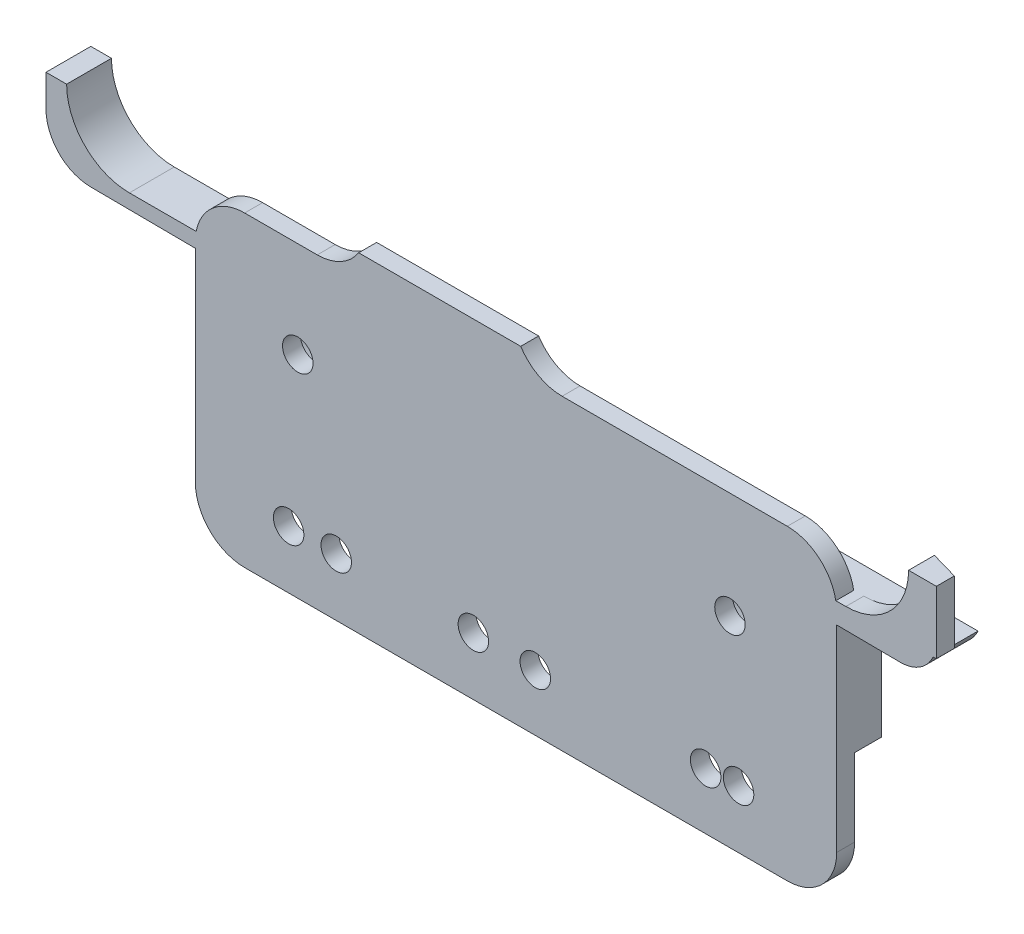
SolidWorks part; units mm, degrees
ref_plane "Plan de face" through (0, 0, 0) normal (0, 0, 1) x (1, 0, 0)
ref_plane "Plan de dessus" through (0, 0, 0) normal (0, 1, 0) x (1, 0, 0)
ref_plane "Plan de droite" through (0, 0, 0) normal (1, 0, 0) x (0, 0, -1)
sketch "Esquisse1" plane through (0, 0, 0) normal (0, 0, 1) x (1, 0, 0)
  line L0 (-101.8864, 22.7193) -> (-64.9263, 22.7193) construction
  line L1 (-68.0864, 83.4017) -> (-68.0864, 71.4017) construction
  line L2 (-118.8906, -27.2807) -> (-47.3665, -27.2807) construction
  line L3 (-120.7144, 72.7193) -> (-45.5428, 72.7193) construction
  line L4 (-83.4864, -42.5983) -> (-83.4864, 89.4017) construction
  line L5 (-56.8564, -27.2807) -> (-56.8564, 72.7193) construction
  line L6 (-110.1164, -27.2807) -> (-110.1164, 72.7193) construction
  line L7 (-59.2664, -27.2807) -> (-59.2664, 72.7193) construction
  line L8 (-56.8564, -13.2807) -> (-110.1164, -13.2807) construction
  line L9 (-64.3564, -27.2807) -> (-64.3564, 72.7193) construction
  line L10 (-110.1164, 36.7193) -> (-56.8564, 36.7193) construction
  line L11 (-56.8564, 66.9393) -> (-110.1164, 66.9393) construction
  line L12 (-91.8564, -27.2807) -> (-91.8564, 72.7193) construction
  line L13 (-107.4664, -27.2807) -> (-107.4664, 72.7193) construction
  line L14 (-56.8564, -14.5207) -> (-110.1164, -14.5207) construction
  line L15 (-110.1164, 60.7193) -> (-56.8564, 60.7193) construction
  line L16 (-117.6801, 66.9393) -> (-117.6801, 59.6951)
  line L17 (-112.1801, 54.1951) -> (-105.2942, 54.1951)
  line L18 (-99.7942, 48.6951) -> (-99.7942, 35.9308)
  line L19 (-113.3906, -38.0606) -> (-52.8665, -38.0606)
  line L20 (-105.2942, -3.8078) -> (-113.3906, -3.8078)
  line L21 (-118.8906, -9.3078) -> (-118.8906, -18.422)
  line L23 (-47.3665, -18.422) -> (-47.3665, -9.3078)
  line L24 (-52.8665, -3.8078) -> (-77.9864, -3.8078)
  line L25 (-83.4864, 1.6922) -> (-83.4864, 12.91)
  line L26 (-77.9864, 60.7193) -> (-54.1904, 60.7193)
  line L27 (-48.6904, 66.2193) -> (-48.6904, 67.2193)
  line L28 (-54.1904, 72.7193) -> (-112.1801, 72.7193)
  line L29 (-117.6801, 67.2193) -> (-117.6801, 66.9393)
  line L30 (-105.2942, 30.4308) -> (-112.1801, 30.4308)
  line L31 (-117.6801, 24.9308) -> (-117.6801, 23.91)
  line L32 (-112.1801, 18.41) -> (-105.2942, 18.41)
  line L33 (-77.9864, 30.4308) -> (-69.8564, 30.4308)
  line L34 (-64.3564, 24.9308) -> (-64.3564, 23.91)
  line L35 (-69.8564, 18.41) -> (-77.9864, 18.41)
  line L36 (-99.7942, 12.91) -> (-99.7942, 1.6922)
  line L37 (-111.3906, 21.4601) -> (-70.0864, 21.4601)
  line L38 (-113.3906, 23.4601) -> (-113.3906, 24.8425)
  line L39 (-111.3906, 26.8425) -> (-70.0864, 26.8425)
  line L40 (-68.0864, 23.4601) -> (-68.0864, 24.8425)
  line L41 (-83.4864, 35.9308) -> (-83.4864, 55.2193)
  line L42 (-118.8906, -18.422) -> (-118.8906, -32.5606)
  line L43 (-47.3665, -18.422) -> (-47.3665, -32.5606)
  circle A0 centre (-59.2664, -15.6637) radius 1.7
  arc A1 (-77.9864, 30.4308) -> (-83.4864, 35.9308) centre (-77.9864, 35.9308) cw
  circle A2 centre (-59.2664, 66.9393) radius 1.7
  circle A3 centre (-91.8564, 36.7193) radius 1.7
  arc A4 (-64.3564, 23.91) -> (-69.8564, 18.41) centre (-69.8564, 23.91) cw
  arc A5 (-112.1801, 72.7193) -> (-117.6801, 67.2193) centre (-112.1801, 67.2193) ccw
  circle A6 centre (-107.4664, -14.5207) radius 1.7
  circle A7 centre (-107.4664, 60.7193) radius 1.7
  arc A8 (-117.6801, 59.6951) -> (-112.1801, 54.1951) centre (-112.1801, 59.6951) ccw
  arc A9 (-105.2942, 54.1951) -> (-99.7942, 48.6951) centre (-105.2942, 48.6951) cw
  arc A10 (-99.7942, 1.6922) -> (-105.2942, -3.8078) centre (-105.2942, 1.6922) cw
  arc A11 (-113.3906, -3.8078) -> (-118.8906, -9.3078) centre (-113.3906, -9.3078) ccw
  arc A14 (-47.3665, -9.3078) -> (-52.8665, -3.8078) centre (-52.8665, -9.3078) ccw
  arc A15 (-77.9864, -3.8078) -> (-83.4864, 1.6922) centre (-77.9864, 1.6922) cw
  arc A16 (-83.4864, 55.2193) -> (-77.9864, 60.7193) centre (-77.9864, 55.2193) cw
  arc A17 (-54.1904, 60.7193) -> (-48.6904, 66.2193) centre (-54.1904, 66.2193) ccw
  arc A18 (-48.6904, 67.2193) -> (-54.1904, 72.7193) centre (-54.1904, 67.2193) ccw
  arc A19 (-69.8564, 30.4308) -> (-64.3564, 24.9308) centre (-69.8564, 24.9308) cw
  arc A20 (-77.9864, 18.41) -> (-83.4864, 12.91) centre (-77.9864, 12.91) ccw
  arc A21 (-105.2942, 18.41) -> (-99.7942, 12.91) centre (-105.2942, 12.91) cw
  arc A22 (-117.6801, 23.91) -> (-112.1801, 18.41) centre (-112.1801, 23.91) ccw
  arc A23 (-112.1801, 30.4308) -> (-117.6801, 24.9308) centre (-112.1801, 24.9308) ccw
  arc A24 (-105.2942, 30.4308) -> (-99.7942, 35.9308) centre (-105.2942, 35.9308) ccw
  arc A25 (-70.0864, 26.8425) -> (-68.0864, 24.8425) centre (-70.0864, 24.8425) cw
  arc A26 (-70.0864, 21.4601) -> (-68.0864, 23.4601) centre (-70.0864, 23.4601) ccw
  arc A27 (-111.3906, 21.4601) -> (-113.3906, 23.4601) centre (-111.3906, 23.4601) cw
  arc A28 (-113.3906, 24.8425) -> (-111.3906, 26.8425) centre (-111.3906, 24.8425) cw
  circle A29 centre (-58.3064, -31.6037) radius 1.7
  circle A30 centre (-108.4864, -31.6007) radius 1.7
  arc A31 (-47.3665, -32.5606) -> (-52.8665, -38.0606) centre (-52.8665, -32.5606) cw
  arc A32 (-118.8906, -32.5606) -> (-113.3906, -38.0606) centre (-113.3906, -32.5606) ccw
  point P61 (-117.6801, 72.7193)
  point P68 (-99.7942, -3.8078)
  point P79 (-83.4864, -3.8078)
  point P82 (-83.4864, 60.7193)
  point P87 (-48.6904, 72.7193)
  point P98 (-83.4864, 30.4308)
  point P101 (-64.3564, 18.41)
  point P104 (-64.3564, 30.4308)
  point P109 (-99.7942, 18.41)
  point P116 (-99.7942, 30.4308)
  dimension "D1" = 5.5
  dimension "D2" = 5.5
  dimension "D3" = 2
  dimension "D8" = 5.5
  dimension "D4" = 15.94
  dimension "D5" = 17.08
  dimension "D6" = 0.96
  dimension "D7" = 1.02
extrude "Boss.-Extru.1" add sketch "Esquisse1" along normal blind 3
sketch "Esquisse2" plane through (0, 0, 0) normal (0, 0, -1) x (-1, 0, 0)
  line L0 (39.3464, 87.1044) -> (39.3464, -42.3137) construction
  line L1 (133.2464, 87.1044) -> (133.2464, 37.9772) construction
  line L2 (59.2664, -15.6637) -> (59.2664, 1.7249) construction
  line L3 (133.2464, -8.2937) -> (39.3464, -8.2937) construction
  line L4 (133.2464, 54.4563) -> (39.3464, 54.4563) construction
  line L5 (126.2464, -8.2937) -> (126.2464, -1.2937) construction
  line L6 (126.2464, -1.2937) -> (133.2464, -1.2937) construction
  line L7 (126.2464, 54.4563) -> (126.2464, 47.4563) construction
  line L8 (126.2464, 47.4563) -> (133.2464, 47.4563) construction
  line L9 (46.3464, 54.4563) -> (46.3464, 47.4563) construction
  line L10 (46.3464, 47.4563) -> (39.3464, 47.4563) construction
  line L11 (39.3464, -1.2937) -> (46.3464, -1.2937) construction
  line L12 (46.3464, -1.2937) -> (46.3464, -8.2937) construction
  line L13 (118.8906, -9.9695) -> (130.5846, -9.8801)
  line L14 (117.6801, 57.0999) -> (130.5464, 57.0999)
  line L15 (47.3665, -10.5841) -> (47.3665, -23.922)
  line L16 (36.2569, 53.0999) -> (36.2569, 47.4563)
  line L17 (36.2569, 47.4563) -> (39.3464, 47.4563)
  line L18 (39.3464, -1.2937) -> (36.2482, -1.2937)
  line L19 (36.2482, -1.2937) -> (36.2482, -6.6454)
  line L20 (40.2828, -10.6453) -> (47.3665, -10.5841)
  line L21 (48.6904, 60.7193) -> (48.6904, 72.7193)
  line L22 (48.6904, 60.7193) -> (48.6904, 57.0999)
  line L23 (126.2464, 54.4563) -> (46.3464, 54.4563)
  line L24 (46.3464, -8.2937) -> (126.2464, -8.2937)
  line L25 (133.2464, 47.4563) -> (133.2464, 40.9772)
  line L26 (48.6904, 72.7193) -> (117.6801, 72.7193)
  line L27 (138.5464, 8.4156) -> (145.7527, 8.4156)
  line L28 (40.2569, 57.0999) -> (48.6904, 57.0999)
  line L29 (148.7527, 11.4156) -> (148.7527, 38.1792)
  line L30 (133.2464, 34.4495) -> (133.2464, -42.3137) construction
  line L32 (117.6801, 72.7193) -> (117.6801, 57.0999)
  line L35 (135.5464, -24.0475) -> (135.5464, 64.4693) construction
  line L36 (47.3665, -32.5606) -> (47.3665, -9.3078) construction
  line L37 (133.2464, 8.3631) -> (133.2464, -1.2937)
  line L38 (47.3665, -23.922) -> (118.8906, -23.922)
  line L39 (118.8906, -23.922) -> (118.8906, -9.9695)
  line L40 (118.8906, -9.3078) -> (118.8906, -32.5606) construction
  line L41 (145.7527, 41.1792) -> (138.5464, 41.1792)
  line L42 (136.2464, 11.3631) -> (142.1623, 11.3631)
  line L43 (145.1623, 14.3631) -> (145.1623, 34.9772)
  line L44 (142.1623, 37.9772) -> (136.2464, 37.9772)
  line L47 (135.5464, -4.8802) -> (135.5464, 5.4156)
  line L57 (135.5464, 44.1792) -> (135.5464, 52.0999)
  arc A0 (133.2464, -1.2937) -> (126.2464, -8.2937) centre (126.2464, -1.2937) cw
  arc A1 (133.2464, 47.4563) -> (126.2464, 54.4563) centre (126.2464, 47.4563) ccw
  arc A2 (46.3464, 54.4563) -> (39.3464, 47.4563) centre (46.3464, 47.4563) ccw
  arc A3 (39.3464, -1.2937) -> (46.3464, -8.2937) centre (46.3464, -1.2937) ccw
  arc A4 (40.2569, 57.0999) -> (36.2569, 53.0999) centre (40.2569, 53.0999) ccw
  arc A5 (148.7527, 38.1792) -> (145.7527, 41.1792) centre (145.7527, 38.1792) ccw
  arc A6 (138.5464, 41.1792) -> (135.5464, 44.1792) centre (138.5464, 44.1792) cw
  arc A7 (136.2464, 37.9772) -> (133.2464, 40.9772) centre (136.2464, 40.9772) cw
  arc A8 (145.1623, 34.9772) -> (142.1623, 37.9772) centre (142.1623, 34.9772) ccw
  arc A9 (142.1623, 11.3631) -> (145.1623, 14.3631) centre (142.1623, 14.3631) ccw
  arc A10 (145.7527, 8.4156) -> (148.7527, 11.4156) centre (145.7527, 11.4156) ccw
  arc A11 (133.2464, 8.3631) -> (136.2464, 11.3631) centre (136.2464, 8.3631) cw
  arc A12 (135.5464, 52.0999) -> (130.5464, 57.0999) centre (130.5464, 52.0999) ccw
  arc A13 (138.5464, 8.4156) -> (135.5464, 5.4156) centre (138.5464, 5.4156) ccw
  arc A15 (130.5846, -9.8801) -> (135.5464, -4.8802) centre (130.5464, -4.8802) ccw
  arc A16 (36.2482, -6.6454) -> (40.2828, -10.6453) centre (40.2482, -6.6454) ccw
  circle A17 centre (59.2664, -15.6637) radius 5.2
  circle A18 centre (107.4664, -14.5207) radius 5.2
  circle A19 centre (107.4664, 60.7193) radius 5.2
  circle A20 centre (59.2664, 66.9393) radius 5.2
  point P34 (135.5464, 57.0999)
  point P37 (132.9964, 22.9063)
  point P43 (132.9964, 22.9063)
  point P45 (133.2464, 29.4495)
  point P50 (133.2464, 16.3631)
  point P62 (111.5444, -10.0296)
  point P71 (64.0892, -10.4396)
  point P74 (135.5464, 26.097)
  point P75 (134.7715, 19.7156)
  point P107 (135.5464, 19.7156)
  point P110 (135.5464, -9.8421)
  dimension "D13" = 4
  dimension "D14" = 3
  dimension "D16" = 5
  dimension "D1" = 19.92
  dimension "D2" = 93.9
  dimension "D3" = 7.37
  dimension "D4" = 62.75
  dimension "D5" = 7
  dimension "D6" = 7
  dimension "D7" = 7
  dimension "D8" = 7
  dimension "D9" = 7
  dimension "D10" = 7
  dimension "D11" = 7
  dimension "D12" = 7
  dimension "D17" = 2.3
extrude "Boss.-Extru.2" add sketch "Esquisse2" along normal blind 3 and the other way blind 3
sketch "Esquisse5" plane through (0, 0, 3) normal (0, 0, 1) x (1, 0, 0)
  line L1 (-156.3908, -45.761) -> (-27.0007, -45.761)
  line L2 (-156.3908, -45.761) -> (-156.3908, 79.8705)
  line L3 (-156.3908, 79.8705) -> (-27.0007, 79.8705)
  line L4 (-27.0007, -45.761) -> (-27.0007, 79.8705)
extrude "Enlèv. mat.-Extru.2" cut sketch "Esquisse5" against normal blind 1
sketch "Esquisse6" plane through (0, 0, 2) normal (0, 0, 1) x (1, 0, 0)
  line L0 (-69.6235, 64.7274) -> (-83.6235, 64.7274) construction
  circle A0 centre (-69.6235, 64.7274) radius 1.5
  circle A1 centre (-83.6235, 64.7274) radius 1.5
extrude "Enlèv. mat.-Extru.3" cut sketch "Esquisse6" against normal blind 8
sketch "Esquisse7" plane through (0, 0, 0) normal (0, 0, -1) x (-1, 0, 0)
  line L0 (47.4608, -8.2937) -> (118.7963, -8.2937) construction
  line L1 (49.8731, -8.2937) -> (35.2624, -8.2937)
  line L2 (49.8731, -8.2937) -> (49.8731, 54.4563)
  line L3 (49.8731, 54.4563) -> (35.2624, 54.4563)
  line L4 (35.2624, -8.2937) -> (35.2624, 54.4563)
  line L5 (113.8548, 54.4563) -> (83.4864, 54.4563) construction
extrude "Enlèv. mat.-Extru.4" cut sketch "Esquisse7" along normal blind 8
sketch "Esquisse9" plane through (0, -1.2937, 0) normal (0, 1, 0) x (1, 0, 0)
  line L0 (-39.3464, -2) -> (-39.3464, 0.886)
  line L1 (-39.3464, 0.886) -> (-36.2482, 0)
  line L2 (-36.2482, 0) -> (-36.2482, -2)
  line L3 (-36.2482, -2) -> (-39.3464, -2)
extrude "Boss.-Extru.3" add sketch "Esquisse9" against normal blind 7
sketch "Esquisse10" plane through (0, 47.4563, 0) normal (0, -1, 0) x (1, 0, 0)
  line L0 (-39.3464, 2) -> (-39.3464, -0.873)
  line L1 (-39.3464, -0.873) -> (-36.2569, 0)
  line L2 (-36.2569, 0) -> (-36.2569, 2)
  line L3 (-36.2569, 2) -> (-39.3464, 2)
extrude "Boss.-Extru.4" add sketch "Esquisse10" against normal blind 7
sketch "Esquisse11" plane through (0, -1.2937, 0) normal (0, 1, 0) x (1, 0, 0)
  line L1 (-24.0918, -6.0718) -> (-167.8991, -6.0718)
  line L2 (-24.0918, -6.0718) -> (-24.0918, 13.8823)
  line L3 (-24.0918, 13.8823) -> (-167.8991, 13.8823)
  line L4 (-167.8991, -6.0718) -> (-167.8991, 13.8823)
extrude "Enlèv. mat.-Extru.5" cut sketch "Esquisse11" along normal blind 89
sketch "Esquisse12" plane through (0, 0, 2) normal (0, 0, 1) x (1, 0, 0)
  line L0 (-108.4864, -31.6007) -> (-58.3064, -31.6037) construction
  circle A0 centre (-103.1759, -31.601) radius 1.7
  circle A1 centre (-87.8859, -31.6019) radius 1.7
  circle A2 centre (-80.9778, -31.7488) radius 1.7
  circle A3 centre (-61.9778, -31.7488) radius 1.7
  dimension "D1" = 15.29
  dimension "D2" = 19
extrude "Enlèv. mat.-Extru.6" cut sketch "Esquisse12" against normal blind 31
